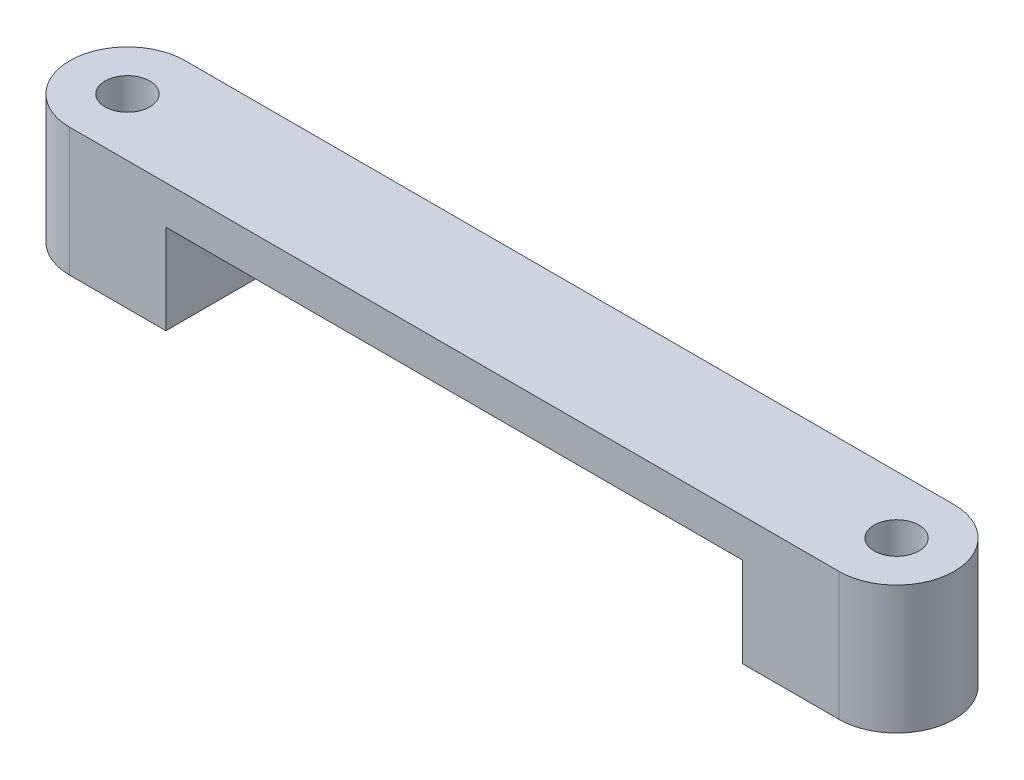
SolidWorks part; units mm, degrees
ref_plane "Front Plane" through (0, 0, 0) normal (0, 0, 1) x (1, 0, 0)
ref_plane "Top Plane" through (0, 0, 0) normal (0, 1, 0) x (1, 0, 0)
ref_plane "Right Plane" through (0, 0, 0) normal (1, 0, 0) x (0, 0, -1)
sketch "Sketch1" plane through (0, 0, 0) normal (0, 1, 0) x (1, 0, 0)
  line L0 (30, 0) -> (-30, 0) construction
  line L1 (30, -4.5) -> (-30, -4.5)
  line L2 (30, 4.5) -> (-30, 4.5)
  arc A0 (30, -4.5) -> (30, 4.5) centre (30, 0) ccw
  arc A1 (-30, 4.5) -> (-30, -4.5) centre (-30, 0) ccw
  circle A2 centre (-30, 0) radius 1.75
  circle A3 centre (30, 0) radius 1.75
  point P3 (0, 0)
  point P12 (0, 0)
  dimension "D2" = 4.5
  dimension "D3" = 3.5
  dimension "D4" = 3.5
  dimension "D1" = 60
extrude "Boss-Extrude1" add sketch "Sketch1" along normal mid plane 10
sketch "Sketch2" plane through (0, 0, 0) normal (0, 0, 1) x (1, 0, 0)
  line L0 (-30, -5) -> (30, -5) construction
  line L1 (-22.5, -5) -> (22.5, -5)
  line L2 (-22.5, -5) -> (-22.5, 2)
  line L3 (-22.5, 2) -> (22.5, 2)
  line L4 (22.5, -5) -> (22.5, 2)
  line L5 (-22.5, -5) -> (22.5, 2) construction
  line L6 (-22.5, 2) -> (22.5, -5) construction
  line L7 (30, 5) -> (-30, 5) construction
  point P4 (0, -1.5)
  dimension "D1" = 45
  dimension "D2" = 3
extrude "Cut-Extrude1" cut sketch "Sketch2" against normal through all both and the other way through all
